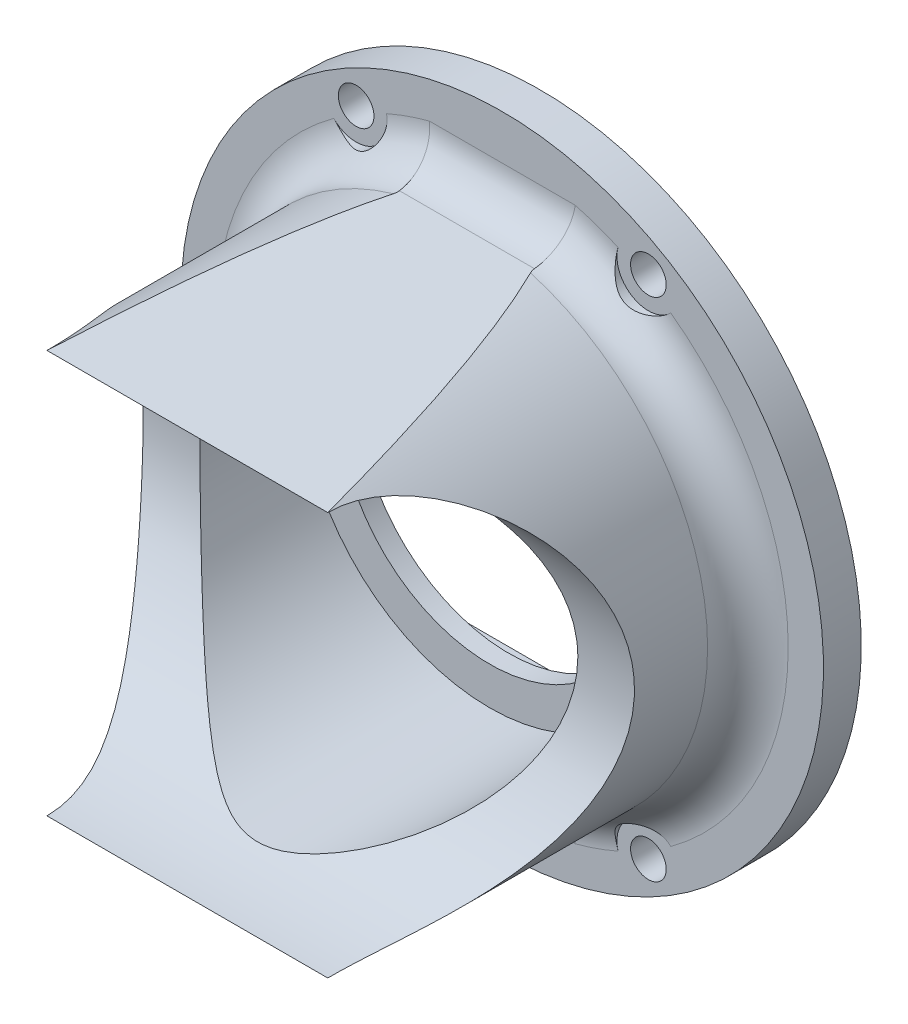
SolidWorks part; units mm, degrees
material "6061-T6 (SS)"
ref_plane "Front Plane" through (0, 0, 0) normal (0, 0, 1) x (1, 0, 0)
ref_plane "Top Plane" through (0, 0, 0) normal (0, 1, 0) x (1, 0, 0)
ref_plane "Right Plane" through (0, 0, 0) normal (1, 0, 0) x (0, 0, -1)
sketch "Sketch1" plane through (0, 0, 0) normal (0, 0, 1) x (1, 0, 0)
  circle A0 centre (0, 0) radius 30.9562
  dimension "D1" = 61.9125
extrude "Boss-Extrude1" add sketch "Sketch1" along normal blind 50.8
sketch "Sketch2" plane through (0, 0, 0) normal (0, 0, -1) x (-1, 0, 0)
  line L1 (-18.3261, -22.2885) -> (18.3261, -22.2885)
  line L2 (-22.2885, -18.3261) -> (-22.2885, 18.3261)
  line L3 (-18.3261, 22.2885) -> (18.3261, 22.2885)
  line L4 (22.2885, -18.3261) -> (22.2885, 18.3261)
  line L5 (-22.2885, -22.2885) -> (22.2885, 22.2885) construction
  line L6 (-22.2885, 22.2885) -> (22.2885, -22.2885) construction
  arc A0 (18.3261, -22.2885) -> (22.2885, -18.3261) centre (18.3261, -18.3261) ccw
  arc A1 (-18.3261, -22.2885) -> (-22.2885, -18.3261) centre (-18.3261, -18.3261) cw
  arc A2 (18.3261, 22.2885) -> (22.2885, 18.3261) centre (18.3261, 18.3261) cw
  arc A3 (-22.2885, 18.3261) -> (-18.3261, 22.2885) centre (-18.3261, 18.3261) cw
  point P0 (0, 0)
  dimension "D3" = 3.9624
  dimension "D1" = 44.577
  dimension "D2" = 44.577
extrude "Cut-Extrude1" cut sketch "Sketch2" against normal blind 3.9624
ref_plane "Plane1" through (30.9562, 0, 0) normal (1, 0, 0) x (0, 0, -1)
sketch "Sketch3" plane through (30.9562, 0, 0) normal (1, 0, 0) x (0, 0, -1)
  line L0 (0, -30.9562) -> (0, 30.9562) construction
  line L1 (-44.45, 25.4) -> (0, 30.9562)
  line L2 (0, 30.9562) -> (-50.8, 30.9562)
  line L3 (-50.8, 30.9562) -> (-50.8, -30.9562)
  line L4 (-50.8, -30.9562) -> (0, -30.9562)
  line L5 (0, -30.9562) -> (-44.45, -25.4)
  arc A0 (-44.45, -25.4) -> (-44.45, 25.4) centre (-44.45, 0) ccw
  dimension "D1" = 50.8
  dimension "D2" = 44.45
extrude "Cut-Extrude2" cut sketch "Sketch3" against normal through all
sketch "Sketch4" plane through (0, 0, 3.9624) normal (0, 0, -1) x (-1, 0, 0)
  circle A0 centre (0, 0) radius 19.05
  dimension "D1" = 38.1
extrude "Cut-Extrude3" cut sketch "Sketch4" against normal through all
ref_plane "Plane2" through (0, 0, 50.8) normal (0, 0, 1) x (1, 0, 0)
sketch "Sketch6" plane through (0, 0, 50.8) normal (0, 0, 1) x (1, 0, 0)
  circle A0 centre (0, 0) radius 23.8125
  dimension "D1" = 47.625
extrude "Cut-Extrude4" cut sketch "Sketch6" against normal blind 44.45
sketch "Sketch7" plane through (0, 0, 3.9624) normal (0, 0, -1) x (-1, 0, 0)
  line L1 (-18.2626, -18.2626) -> (18.2626, -18.2626) construction
  line L2 (-18.2626, -18.2626) -> (-18.2626, 18.2626) construction
  line L3 (-18.2626, 18.2626) -> (18.2626, 18.2626) construction
  line L4 (18.2626, -18.2626) -> (18.2626, 18.2626) construction
  line L5 (-18.2626, -18.2626) -> (18.2626, 18.2626) construction
  line L6 (-18.2626, 18.2626) -> (18.2626, -18.2626) construction
  point P0 (0, 0)
  dimension "D1" = 36.5252
  dimension "D2" = 36.5252
hole_wizard "#4-40 Tapped Hole1" positions "Sketch9" profile "Sketch8" tap size "#4-40" standard "Ansi Inch"
sketch "Sketch9" plane through (0, 0, 3.9624) normal (0, 0, -1) x (-1, 0, 0)
  point P0 (-18.2626, 18.2626)
  point P1 (18.2626, 18.2626)
  point P4 (18.2626, -18.2626)
  point P7 (-18.2626, -18.2626)
sketch "Sketch8" plane through (18.2626, 18.2626, 3.9624) normal (1, 0, 0) x (0, 1, 0)
  line L0 (0, 0) -> (0, 8.2992)
  line L1 (0, 8.2992) -> (1.1303, 7.62)
  line L2 (1.1303, 7.62) -> (1.1303, 0)
  line L5 (1.1303, 0) -> (0, 0)
  line L10 (0, 8.2992) -> (-1.1303, 7.62) construction
  line L11 (0, -6.35) -> (0, 107.95) construction
  dimension "Tap Drill Dia." = 2.2606
  dimension "Tap Drill Depth" = 7.62
  dimension "Drill Angle" = 118
cosmetic thread "Hole Thread1" parameters "D1"=5.588, "D2"=2.8448
cosmetic thread "Hole Thread2" parameters "D1"=5.588, "D2"=2.8448
cosmetic thread "Hole Thread3" parameters "D1"=5.588, "D2"=2.8448
cosmetic thread "Hole Thread4" parameters "D1"=5.588, "D2"=2.8448
sketch "Sketch10" plane through (0, 0, 0) normal (0, 0, -1) x (-1, 0, 0)
  line L0 (-17.6955, 25.4) -> (17.6955, 25.4)
  line L1 (-17.6955, -25.4) -> (17.6955, -25.4)
  arc A0 (-17.6955, 25.4) -> (-17.6955, -25.4) centre (0, 0) ccw
  arc A1 (0, 30.9563) -> (0, -30.9562) centre (0, 0) ccw construction
  circle A2 centre (0, 0) radius 40.4813
  arc A3 (17.6955, -25.4) -> (17.6955, 25.4) centre (0, 0) ccw
  dimension "D1" = 9.525
  dimension "D2" = 25.4
extrude "Boss-Extrude3" add sketch "Sketch10" against normal blind 4.7625
sketch "Sketch12" plane through (0, 0, 4.7625) normal (0, 0, 1) x (1, 0, 0)
  circle A0 centre (0, 0) radius 36.83 construction
  dimension "D1" = 73.66
fillet "Fillet1" radius 5.08 4 edges at (30.9562, 0, 4.7625) (-30.9562, 0, 4.7625) (0, -30.3609, 4.7625) (0, 30.3609, 4.7625)
hole_wizard "#8 Clearance Hole1" positions "Sketch14" profile "Sketch13" hole size "#8" standard "Ansi Inch"
sketch "Sketch14" plane through (0, 0, 4.7625) normal (0, 0, 1) x (1, 0, 0)
  line L0 (0, 0) -> (0, 40.4813) construction
  line L2 (0, 0) -> (-18.415, 31.8957) construction
  circle A0 centre (0, 0) radius 36.83 construction
  circle A1 centre (0, 0) radius 40.4813 construction
  point P0 (-18.415, 31.8957)
  dimension "D1" = 30
sketch "Sketch13" plane through (-18.415, 31.8957, 4.7625) normal (1, 0, 0) x (0, -1, 0)
  line L0 (0, 0) -> (0, 26.7507)
  line L1 (0, 26.7507) -> (2.2479, 25.4)
  line L2 (2.2479, 25.4) -> (2.2479, 0)
  line L5 (2.2479, 0) -> (0, 0)
  line L10 (0, 26.7507) -> (-2.2479, 25.4) construction
  line L11 (0, -6.35) -> (0, 107.95) construction
  dimension "Hole Dia." = 4.4958
  dimension "Hole Depth" = 25.4
  dimension "Drill Angle" = 118
pattern_circular "CirPattern1" count 2 every 60 about axis through (0, 0, 4.7625) along (0, 0, -1) of "#8 Clearance Hole1"
ref_plane "Plane3" through (0, 0, 9.8425) normal (0, 0, 1) x (1, 0, 0)
mirror "Mirror1" about plane through (0, 0, 0) normal (0, 1, 0) of "CirPattern1", "#8 Clearance Hole1"
sketch "Sketch15" plane through (0, 0, 9.8425) normal (0, 0, 1) x (1, 0, 0)
  circle A0 centre (-18.415, 31.8957) radius 3.9624
  circle A1 centre (18.415, 31.8957) radius 3.9624
  circle A3 centre (18.415, -31.8957) radius 3.9624
  circle A4 centre (-18.415, -31.8957) radius 3.9624
  dimension "D1" = 7.9248
extrude "Cut-Extrude5" cut sketch "Sketch15" against normal up to surface (5.08 mm away) up to face at (-40.4813, 0, 4.7625)
